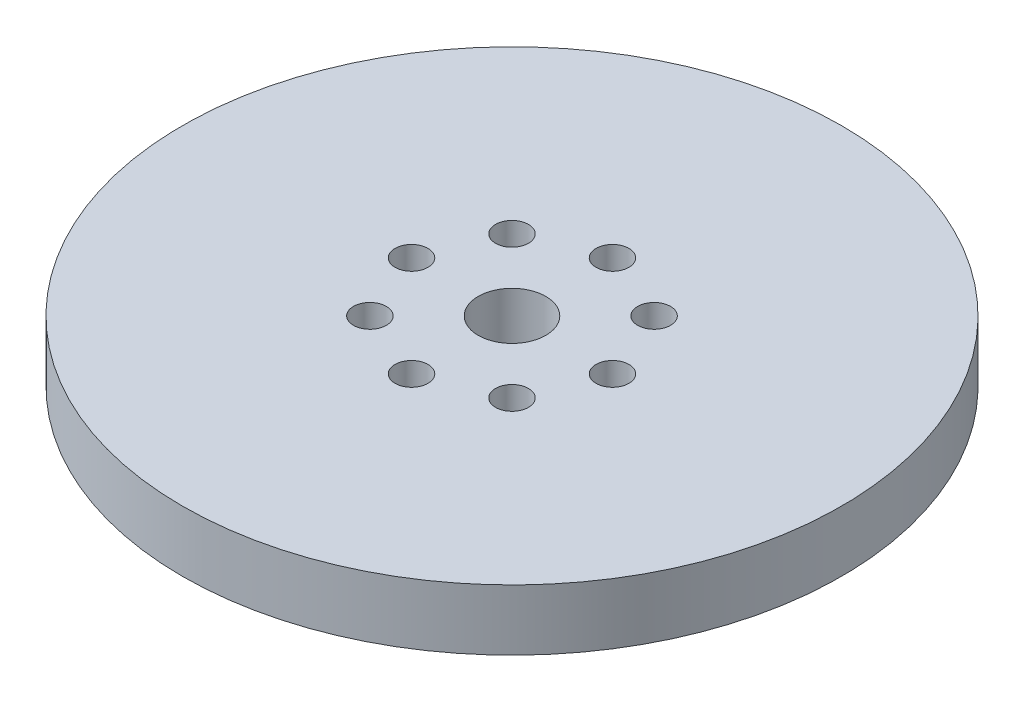
SolidWorks part; units mm, degrees
ref_plane "Front Plane" through (0, 0, 0) normal (0, 0, 1) x (1, 0, 0)
ref_plane "Top Plane" through (0, 0, 0) normal (0, 1, 0) x (1, 0, 0)
ref_plane "Right Plane" through (0, 0, 0) normal (1, 0, 0) x (0, 0, -1)
sketch "Sketch1" plane through (0, 0, 0) normal (0, 1, 0) x (1, 0, 0)
  circle A0 centre (0, 0) radius 97.5
  dimension "FLANGE_OD" = 195
extrude "Boss-Extrude1" add sketch "Sketch1" along normal blind 18
sketch "Sketch2" plane through (0, 0, 0) normal (0, 1, 0) x (1, 0, 0)
  circle A0 centre (0, 0) radius 10
  dimension "BORE_D" = 20
extrude "Cut-Extrude1" cut sketch "Sketch2" along normal through all
sketch "Sketch3" plane through (0, 18, 0) normal (0, 1, 0) x (1, 0, 0)
  circle A0 centre (0, 0) radius 29.7256 construction
  circle A1 centre (-29.7256, 0) radius 4.8651
  dimension "BOLT_D" = 9.7303
  dimension "BOLT_PCD" = 59.4511
extrude "Cut-Extrude2" cut sketch "Sketch3" against normal blind 14.6734
pattern_circular "CirPattern1" count 8 over 360 about axis through (0, 0, 0) along (0, 1, 0) of "Cut-Extrude2"
